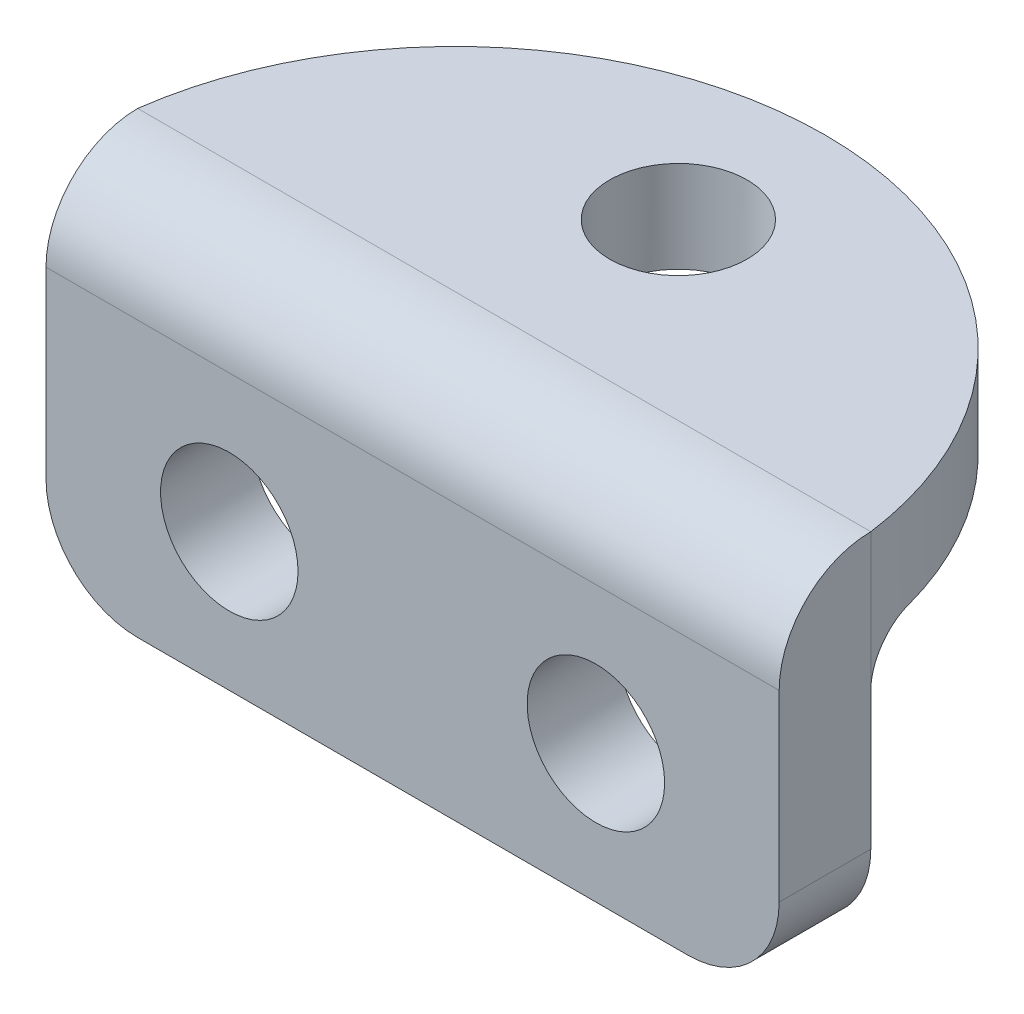
SolidWorks part; units mm, degrees
ref_plane "Front Plane" through (0, 0, 0) normal (0, 0, 1) x (1, 0, 0)
ref_plane "Top Plane" through (0, 0, 0) normal (0, 1, 0) x (1, 0, 0)
ref_plane "Right Plane" through (0, 0, 0) normal (1, 0, 0) x (0, 0, -1)
sketch "Sketch14" plane through (0, 0, 0) normal (1, 0, 0) x (0, 0, -1)
  line L0 (9.4803, -6.1219) -> (9.4803, 1.8781)
  line L1 (9.4803, 1.8781) -> (18.4803, 1.8781)
  line L2 (18.4803, 1.8781) -> (18.4803, -0.1219)
  line L3 (18.4803, -0.1219) -> (11.4803, -0.1219)
  line L4 (11.4803, -0.1219) -> (11.4803, -6.1219)
  line L5 (11.4803, -6.1219) -> (9.4803, -6.1219)
  dimension "D1" = 2
  dimension "D2" = 2
  dimension "D3" = 9
  dimension "D4" = 8
extrude "Boss-Extrude4" add sketch "Sketch14" along normal blind 16 separate body contours L5 L4 L3 L2 L1 L0 region at (0, -2.1219, -9.6007)
sketch "Sketch15" plane through (0, -0.1219, 0) normal (0, -1, 0) x (1, 0, 0)
  line L3 (8, -9.4803) -> (8, -18.4803) construction
  line L4 (16, -9.4803) -> (0, -9.4803) construction
  line L5 (16, -11.4803) -> (0, -11.4803) construction
  line L6 (16, -18.4803) -> (0, -18.4803) construction
  line L11 (0, -11.4803) -> (0, -18.4803)
  line L12 (0, -18.4803) -> (16, -18.4803)
  line L13 (16, -18.4803) -> (16, -11.4803)
  line L14 (16, -11.4803) -> (0, -11.4803)
  line L15 (0, -11.4803) -> (0, -18.4803)
  line L16 (0, -18.4803) -> (16, -18.4803)
  line L17 (16, -18.4803) -> (16, -11.4803)
  line L18 (16, -11.4803) -> (0, -11.4803)
  arc A1 (0, -11.4803) -> (16, -11.4803) centre (8, -10.4089) ccw
  point P14 (8, -18.4803)
  line M7 (0, -11.4803) -> (0, -18.4803)
  line M8 (0, -18.4803) -> (16, -18.4803)
  line M9 (16, -18.4803) -> (16, -11.4803)
  dimension "D1" = 0
extrude "Cut-Extrude3" cut sketch "Sketch15" against normal blind 16 contours A1 M7 M8 | A1 L16 M9 region at (1.8005, -0.1219, -16.7508) region at (14.1995, -0.1219, -16.7508)
sketch "Sketch16" plane through (0, 0, -9.4803) normal (0, 0, 1) x (1, 0, 0)
  line L0 (16, -6.1219) -> (16, 1.8781) construction
  line L1 (0, -6.1219) -> (0, 1.8781) construction
  line L2 (16, -6.1219) -> (0, -6.1219) construction
  circle A0 centre (4, -3.1219) radius 1.5
  circle A1 centre (12, -3.1219) radius 1.5
  dimension "D1" = 3
  dimension "D2" = 4
  dimension "D3" = 4
  dimension "D4" = 3
  dimension "D5" = 3
extrude "Cut-Extrude4" cut sketch "Sketch16" against normal blind 16
fillet "Fillet1" radius 2 2 edges at (16, -6.1219, -10.4803) (0, -6.1219, -10.4803)
fillet "Fillet2" radius 2 1 edges at (8, 1.8781, -9.4803)
sketch "Sketch17" plane through (0, 1.8781, 0) normal (0, 1, 0) x (1, 0, 0)
  line L0 (-0.7049, 15.2803) -> (17.0513, 15.2803) construction
  line L1 (16, 9.4803) -> (0, 9.4803) construction
  line L2 (8, 18.4803) -> (8, 15.2803) construction
  arc A0 (16, 11.4803) -> (0, 11.4803) centre (8, 10.4089) ccw construction
  circle A2 centre (8, 15.2803) radius 1.5
  dimension "D2" = 3
  dimension "D1" = 5.8
extrude "Cut-Extrude5" cut sketch "Sketch17" against normal blind 16
fillet "Fillet3" radius 1 1 edges at (8, -0.1219, -11.4803)
